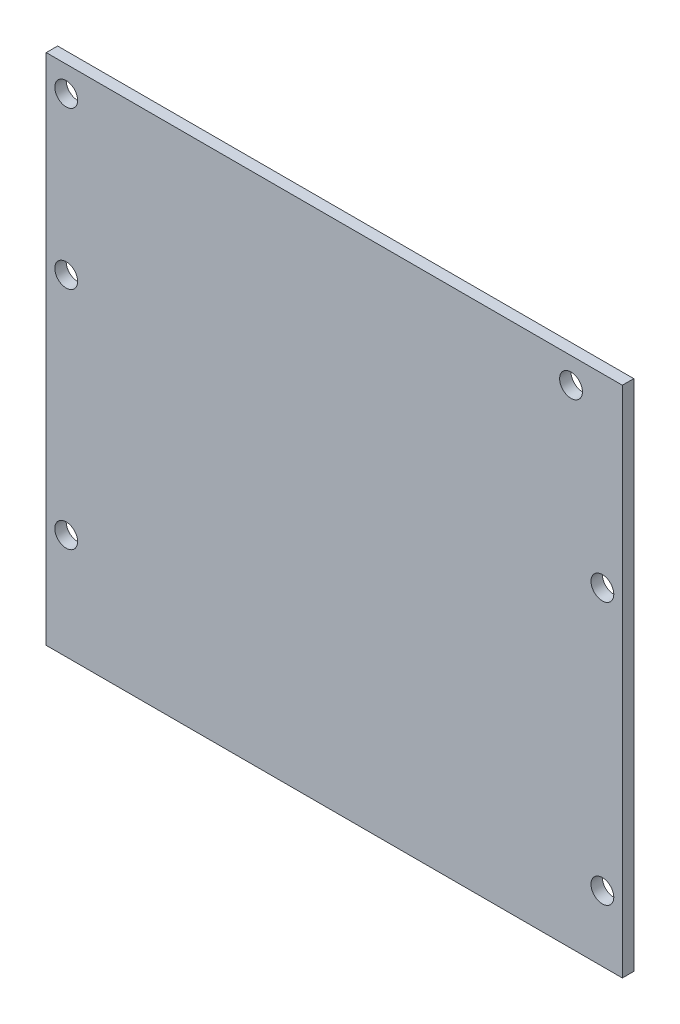
SolidWorks part; units mm, degrees
ref_plane "Plan de face" through (0, 0, 0) normal (0, 0, 1) x (1, 0, 0)
ref_plane "Plan de dessus" through (0, 0, 0) normal (0, 1, 0) x (1, 0, 0)
ref_plane "Plan de droite" through (0, 0, 0) normal (1, 0, 0) x (0, 0, -1)
sketch "Esquisse1" plane through (0, 0, 0) normal (0, 0, 1) x (1, 0, 0)
  line L1 (0, 0) -> (101, 0)
  line L2 (0, 0) -> (0, 90)
  line L3 (0, 90) -> (101, 90)
  line L4 (101, 0) -> (101, 90)
  dimension "D1" = 90
  dimension "D2" = 101
extrude "Boss.-Extru.1" add sketch "Esquisse1" along normal blind 2
sketch "Hole Sketch" plane through (0, 0, 2) normal (0, 0, 1) x (1, 0, 0)
  line L0 (0, 0) -> (101, 0) construction
  line L1 (101, 0) -> (101, 90) construction
  line L2 (0, 90) -> (0, 0) construction
  circle A0 centre (97.5, 11.5) radius 2
  circle A1 centre (97.5, 57.5) radius 2
  circle A2 centre (3.5, 18.5) radius 2
  circle A3 centre (3.5, 58) radius 2
  circle A4 centre (3.5, 85.5) radius 2
  circle A5 centre (92, 85.5) radius 2
  dimension "D1" = 4
  dimension "D2" = 11.5
  dimension "D3" = 3.5
  dimension "D4" = 57.5
  dimension "D5" = 3.5
  dimension "D6" = 18.5
  dimension "D7" = 58
  dimension "D8" = 85.5
  dimension "D9" = 9
extrude "Enlèv. mat.-Extru.1" cut sketch "Hole Sketch" against normal through all
